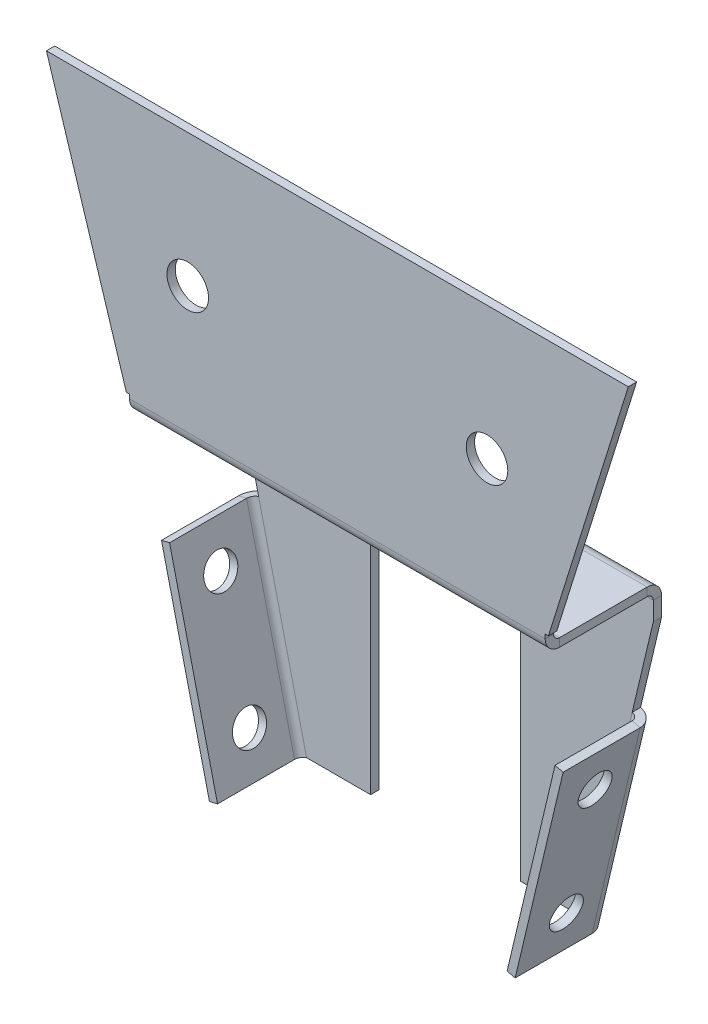
SolidWorks part; units mm, degrees
note: The reader was unsure of these and kept them because the rebuilt part matched: flange length of "Kenar-Flanş1", "Kenar-Flanş2", "Kenar-Flanş3".
ref_plane "Ön Düzlem" through (0, 0, 0) normal (0, 0, 1) x (1, 0, 0)
ref_plane "Üst Düzlem" through (0, 0, 0) normal (0, 1, 0) x (1, 0, 0)
ref_plane "Sağ Düzlem" through (0, 0, 0) normal (1, 0, 0) x (0, 0, -1)
sketch "Çizim1" plane through (0, 0, 0) normal (0, 0, 1) x (1, 0, 0)
  line L0 (-25, 16) -> (25, -16) construction
  line L1 (-25, 16) -> (25, 16)
  line L3 (-25, -16) -> (25, -16)
  line L5 (-25, 16) -> (-35, 16)
  line L6 (-35, 16) -> (-25, -16)
  line L7 (0, -16) -> (0, 16) construction
  line L8 (25, 16) -> (35, 16)
  line L9 (35, 16) -> (25, -16)
  circle A0 centre (-18, 0) radius 2.5
  circle A1 centre (18, 0) radius 2.5
  dimension "D3" = 18
  dimension "D4" = 18
  dimension "D1" = 32
  dimension "D2" = 50
  dimension "D5" = 10
base flange "Taban-Flanş1" sketch "Çizim1" thickness 1 reverse thickness direction no parameters "D1"=0.7366
edge flange "Kenar-Flanş1" sketch "Çizim4" flange angle 90 flange length 13 flange position material outside bend radius 0.7366 thickness 1 relief rectangular parameters "D6"=10
sketch "Çizim4" plane through (0, -16, -1) normal (0, -1, 0) x (-1, 0, 0)
  line L0 (25, 0) -> (-25, 0) construction
  line L1 (25, 0) -> (-25, 0)
  line L2 (-25, 0) -> (-25, 12)
  line L3 (-25, 12) -> (-9, 12)
  line L4 (25, 12) -> (25, 0)
  line L5 (9, 12) -> (25, 12)
  line L6 (25, 12) -> (-25, 12) construction
  arc A0 (-9, 12) -> (9, 12) centre (0, 12) ccw
  dimension "D1" = 18
bend "KenarBükümü1" bend radius 0.7366 bend angle 90 parameters "D5"=1
edge flange "Kenar-Flanş2" sketch "Çizim9" flange profiles "Çizim9", "Çizim10" flange angle 90 flange length 39 flange position material outside bend radius 0.7366 thickness 1 relief rectangular parameters "D6"=10, "D8"=1
sketch "Çizim9" plane through (0, -17, -13) normal (0, 0, -1) x (1, 0, 0)
  line L0 (9, 0) -> (25, 0) construction
  line L1 (9, 0) -> (25, 0)
  line L2 (9, 0) -> (9, 38)
  line L3 (9, 38) -> (25, 38)
  line L4 (25, 38) -> (25, 0)
sketch "Çizim10" plane through (0, -17, -13) normal (0, 0, -1) x (1, 0, 0)
  line L0 (-25, 0) -> (-9, 0) construction
  line L1 (-25, 0) -> (-9, 0)
  line L2 (-25, 0) -> (-25, 38)
  line L3 (-25, 38) -> (-9, 38)
  line L4 (-9, 38) -> (-9, 0)
bend "KenarBükümü2" bend radius 0.7366 bend angle 90 parameters "D5"=2
bend "KenarBükümü3" bend radius 0.7366 bend angle 90 parameters "D5"=3
sketch "Çizim11" plane through (0, 0, -14) normal (0, 0, -1) x (-1, 0, 0)
  line L0 (-16.7, -55) -> (-25, -20)
  line L1 (-25, -55) -> (-9, -55) construction
  line L2 (-25, -17.7366) -> (-25, -55) construction
  line L3 (-25, -20) -> (-25, -55)
  line L4 (-25, -55) -> (-16.7, -55)
  line L5 (0, -55) -> (0, -25.3657) construction
  line L6 (25, -55) -> (16.7, -55)
  line L7 (25, -20) -> (25, -55)
  line L8 (16.7, -55) -> (25, -20)
  dimension "D1" = 8.3
  dimension "D2" = 35
extrude "Kes-Ekstrüzyon1" cut sketch "Çizim11" against normal blind 10 normal cut yes
edge flange "Kenar-Flanş3" sketch "Çizim14" flange profiles "Çizim14", "Çizim16" flange angle 90 flange length 11 flange position bend outside bend radius 0.7366 thickness 1 relief rectangular parameters "D6"=10, "D8"=1
sketch "Çizim14" plane through (28.1593, -6.6778, -13) normal (0.973, -0.2307, 0) x (0.2307, 0.973, 0)
  line L2 (-49.6624, 0) -> (-49.6624, 10)
  line L3 (-49.6624, 10) -> (-24.6624, 10)
  line L5 (-13.6917, 0) -> (-49.6624, 0) construction
  line L6 (-24.6624, 0) -> (-49.6624, 0)
  line L7 (-24.6624, 10) -> (-24.6624, 0)
  circle A0 centre (-44.6624, 5) radius 2
  circle A1 centre (-29.6624, 5) radius 2
  point P11 (-46.7221, 6.1765)
  dimension "D2" = 15
  dimension "D1" = 25
  dimension "D3" = 5
  dimension "D4" = 5
  dimension "D5" = 10
sketch "Çizim16" plane through (-28.1593, -6.6778, -13) normal (-0.973, -0.2307, 0) x (0.2307, -0.973, 0)
  line L0 (49.6624, 0) -> (13.6917, 0) construction
  line L1 (49.6624, 0) -> (24.6624, 0)
  line L3 (24.6624, 10) -> (49.6624, 10)
  line L4 (49.6624, 10) -> (49.6624, 0)
  line L5 (24.6624, 0) -> (24.6624, 10)
  circle A0 centre (29.6624, 5) radius 2
  circle A1 centre (44.6624, 5) radius 2
  dimension "D2" = 15
  dimension "D1" = 25
  dimension "D3" = 5
  dimension "D4" = 5
  dimension "D5" = 10
bend "KenarBükümü4" bend radius 0.7366 bend angle 90 parameters "D5"=4
bend "KenarBükümü5" bend radius 0.7366 bend angle 90 parameters "D5"=6
sketch "Büküm-Çizgileri1" [suppressed] plane through (0, 0, 0) normal (0, 1, 0) x (1, 0, 0)
sketch "Sınırlandırma-Kutusu1" [suppressed] plane through (0, 0, 0) normal (0, 1, 0) x (1, 0, 0)
sheet metal parameters "Sac-Levha1" thickness 1 parameters "D1"=0.7366
flat pattern "Düz-Çoğaltma1" [suppressed]
sketch "Büküm-Çizgileri2" plane through (0, 0, 0) normal (0, 1, 0) x (1, 0, 0)
sketch3d "Sınırlandırma-Kutusu2" [suppressed]
  line L0 (25, -16, 0) -> (-25, -16, 0) construction
  line L1 (25, 16, 0) -> (-25, 16, 0) construction
  line L2 (25, -16, 0) -> (25, 16, 0) construction
  line L3 (-25, -16, 0) -> (-25, 16, 0) construction
sheet metal parameters "Sac-Levha2" thickness 1 parameters "D1"=0.7366
flat pattern "Düz-Çoğaltma1"
sketch "Büküm-Çizgileri2" plane through (0, 0, 0) normal (0, 0, 1) x (1, 0, 0)
  line L0 (-25, -16.2346) -> (25, -16.2346) construction
  line L1 (-25, -16.2346) -> (25, -16.2346) construction
sketch3d "Sınırlandırma-Kutusu2" [suppressed]
  line L0 (-25, -28.4692, 0) -> (25, -28.4692, 0) construction
  line L1 (-25, 16, 0) -> (25, 16, 0) construction
  line L2 (-25, -28.4692, 0) -> (-25, 16, 0) construction
  line L3 (25, -28.4692, 0) -> (25, 16, 0) construction
bend of the flat pattern "Düzleştirme TipiKenarBükümü1>1"
sheet metal parameters "Sac-Levha3" thickness 1 parameters "D1"=0.7366
flat pattern "Düz-Çoğaltma1"
sketch "Büküm-Çizgileri2" plane through (0, 0, 0) normal (0, 0, 1) x (1, 0, 0)
  line L0 (-25, -16.2346) -> (25, -16.2346) construction
  line L1 (-25, -16.2346) -> (25, -16.2346) construction
  line L2 (-25, -28.7039) -> (-9, -28.7039) construction
  line L3 (9, -28.7039) -> (25, -28.7039) construction
  line L4 (-25, -28.7039) -> (-9, -28.7039) construction
  line L5 (9, -28.7039) -> (25, -28.7039) construction
sketch3d "Sınırlandırma-Kutusu2" [suppressed]
  line L0 (25, 16, 0) -> (25, -66.9385, 0) construction
  line L1 (-25, 16, 0) -> (-25, -66.9385, 0) construction
  line L2 (25, 16, 0) -> (-25, 16, 0) construction
  line L3 (25, -66.9385, 0) -> (-25, -66.9385, 0) construction
bend of the flat pattern "Düzleştirme TipiKenarBükümü1>1"
bend of the flat pattern "Düzleştirme TipiKenarBükümü2>1"
bend of the flat pattern "Düzleştirme TipiKenarBükümü3>1"
sheet metal parameters "Sac-Levha4" thickness 1 parameters "D1"=0.7366
flat pattern "Düz-Çoğaltma1"
sketch "Büküm-Çizgileri2" plane through (0, 0, 0) normal (0, 0, 1) x (1, 0, 0)
  line L0 (-25, -16.2346) -> (25, -16.2346) construction
  line L1 (-25, -16.2346) -> (25, -16.2346) construction
  line L2 (-25, -28.7039) -> (-9, -28.7039) construction
  line L3 (9, -28.7039) -> (25, -28.7039) construction
  line L4 (-25, -28.7039) -> (-9, -28.7039) construction
  line L5 (9, -28.7039) -> (25, -28.7039) construction
sketch3d "Sınırlandırma-Kutusu2" [suppressed]
  line L0 (35, 16, 0) -> (35, -66.9385, 0) construction
  line L1 (-35, 16, 0) -> (-35, -66.9385, 0) construction
  line L2 (35, 16, 0) -> (-35, 16, 0) construction
  line L3 (35, -66.9385, 0) -> (-35, -66.9385, 0) construction
bend of the flat pattern "Düzleştirme TipiKenarBükümü1>1"
bend of the flat pattern "Düzleştirme TipiKenarBükümü2>1"
bend of the flat pattern "Düzleştirme TipiKenarBükümü3>1"
sheet metal parameters "Sac-Levha5" thickness 1 parameters "D1"=0.7366
flat pattern "Düz-Çoğaltma1"
sketch "Büküm-Çizgileri2" plane through (0, 0, 0) normal (0, 0, 1) x (1, 0, 0)
  line L0 (-25, -16.2346) -> (25, -16.2346) construction
  line L1 (-25, -16.2346) -> (25, -16.2346) construction
  line L2 (-25, -28.7039) -> (-9, -28.7039) construction
  line L3 (9, -28.7039) -> (25, -28.7039) construction
  line L4 (-25, -28.7039) -> (-9, -28.7039) construction
  line L5 (9, -28.7039) -> (25, -28.7039) construction
  line L6 (17.645, -67.1626) -> (23.4136, -42.8372) construction
  line L7 (17.645, -67.1626) -> (23.4136, -42.8372) construction
  line L8 (-23.4136, -42.8372) -> (-17.645, -67.1626) construction
  line L9 (-23.4136, -42.8372) -> (-17.645, -67.1626) construction
sketch3d "Sınırlandırma-Kutusu2" [suppressed]
  line L0 (35, 16, 0) -> (35, -69.5242, 0) construction
  line L1 (-35, 16, 0) -> (-35, -69.5242, 0) construction
  line L2 (35, 16, 0) -> (-35, 16, 0) construction
  line L3 (35, -69.5242, 0) -> (-35, -69.5242, 0) construction
bend of the flat pattern "Düzleştirme TipiKenarBükümü1>1"
bend of the flat pattern "Düzleştirme TipiKenarBükümü2>1"
bend of the flat pattern "Düzleştirme TipiKenarBükümü3>1"
bend of the flat pattern "Düzleştirme TipiKenarBükümü4>1"
bend of the flat pattern "Düzleştirme TipiKenarBükümü5>1"
